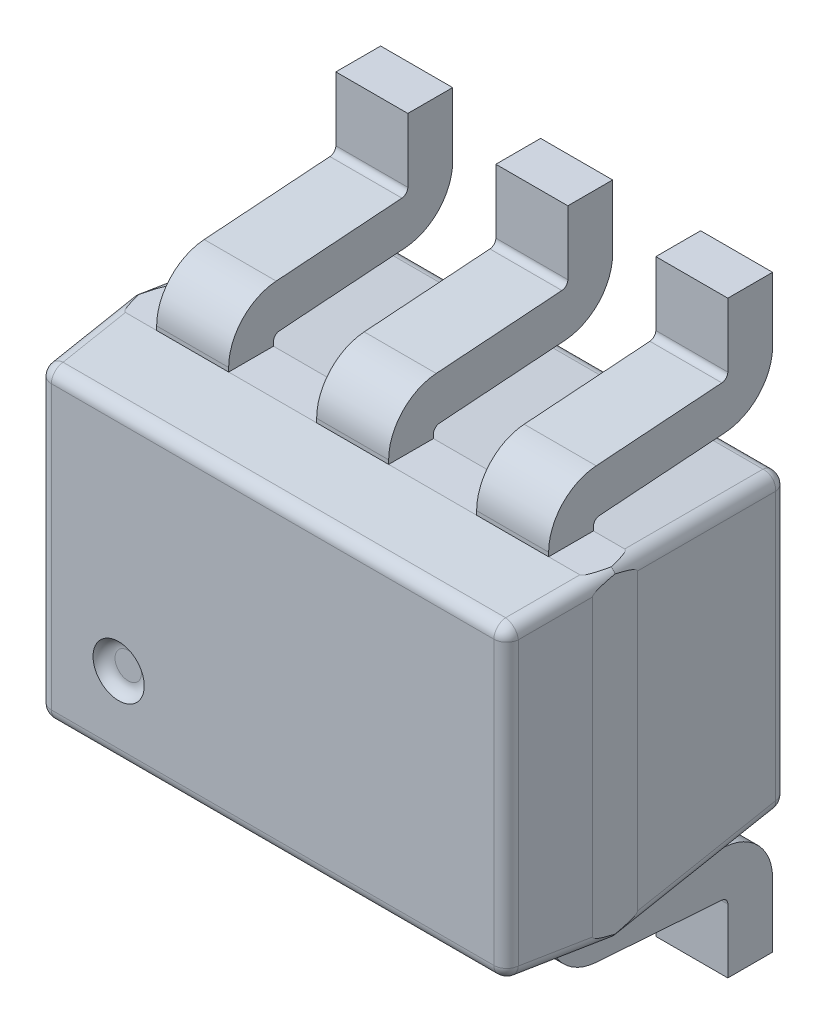
SolidWorks part; units mm, degrees
ref_plane "Alzado" through (0, 0, 0) normal (0, 0, 1) x (1, 0, 0)
ref_plane "Planta" through (0, 0, 0) normal (0, 1, 0) x (1, 0, 0)
ref_plane "Vista lateral" through (0, 0, 0) normal (1, 0, 0) x (0, 0, -1)
sketch "Croquis1" plane through (0, 0, 0) normal (0, 0, 1) x (1, 0, 0)
  line L1 (-0.75, -0.5) -> (0.75, -0.5)
  line L2 (-0.75, -0.5) -> (-0.75, 0.5)
  line L3 (-0.75, 0.5) -> (0.75, 0.5)
  line L4 (0.75, -0.5) -> (0.75, 0.5)
  line L5 (-0.75, -0.5) -> (0.75, 0.5) construction
  line L6 (-0.75, 0.5) -> (0.75, -0.5) construction
  point P0 (0, 0)
  dimension "D1" = 1
  dimension "D2" = 1.5
extrude "Saliente-Extruir1" add sketch "Croquis1" along normal blind 0.51 from offset 0.05
chamfer "Chaflán1" distance 0.51 angle 5 4 edges at (0, 0.5, 0.05) (0, -0.5, 0.05) (-0.75, 0, 0.05) (0.75, 0, 0.05) first distance on face at (0, 0.5, 0.305) first distance on face at (0, -0.5, 0.305) first distance on face at (-0.75, 0, 0.305) first distance on face at (0.75, 0, 0.305)
sketch "Croquis2" plane through (0, 0, 0.56) normal (0, 0, 1) x (1, 0, 0)
  line L1 (-0.75, -0.5) -> (0.75, -0.5)
  line L2 (-0.75, -0.5) -> (-0.75, 0.5)
  line L3 (-0.75, 0.5) -> (0.75, 0.5)
  line L4 (0.75, -0.5) -> (0.75, 0.5)
  line L5 (-0.75, -0.5) -> (0.75, 0.5) construction
  line L6 (-0.75, 0.5) -> (0.75, -0.5) construction
  point P0 (0, 0)
extrude "Saliente-Extruir2" add sketch "Croquis2" along normal blind 0.39
chamfer "Chaflán2" distance 0.25 angle 5 4 edges at (-0.75, 0, 0.95) (0, -0.5, 0.95) (0.75, 0, 0.95) (0, 0.5, 0.95) first distance on face at (-0.75, 0, 0.755) first distance on face at (0, -0.5, 0.755) first distance on face at (0.75, 0, 0.755) first distance on face at (0, 0.5, 0.755)
fillet "Redondeo1" radius 0.04 16 edges at (0, 0.4554, 0.05) (-0.7054, 0, 0.05) (0, -0.4554, 0.05) (0.7054, 0, 0.05) (0.7281, 0, 0.95) (0, -0.4781, 0.95) (-0.7281, 0, 0.95) (0, 0.4781, 0.95) (0.7277, -0.4777, 0.305) (0.7391, -0.4891, 0.825) (0.7391, 0.4891, 0.825) (0.7277, 0.4777, 0.305) (-0.7277, 0.4777, 0.305) (-0.7391, 0.4891, 0.825) (-0.7277, -0.4777, 0.305) (-0.7391, -0.4891, 0.825)
sketch "Croquis4" plane through (0, 0, 0) normal (1, 0, 0) x (0, 0, -1)
  line L0 (-0.56, -0.495) -> (-0.56, -0.5124)
  line L1 (-0.5414, -0.5323) -> (-0.1486, -0.5604)
  line L2 (0, -0.72) -> (0, -0.92)
  line L3 (0, 0) -> (-0.7594, 0) construction
  arc A0 (-0.1486, -0.5604) -> (0, -0.72) centre (-0.16, -0.72) cw
  arc A1 (-0.56, -0.5124) -> (-0.5414, -0.5323) centre (-0.54, -0.5124) ccw
  point P9 (0, -0.571)
  point P12 (-0.56, -0.531)
  dimension "D5" = 0.2
  dimension "D1" = 0.425
  dimension "D2" = 0.16
  dimension "D6" = 0.02
  dimension "D3" = 0.076
  dimension "D4" = 0.04
extrude "Extruir-Lámina1" add sketch "Croquis4" along normal mid plane 0.225 thin thin type one direction wall 0.14
pattern_linear "MatrizL2" count 2 spacing 0.5 along (1, 0, 0) count 2 spacing 0.5 along (-1, 0, 0) of "Extruir-Lámina1"
mirror "Simetría2" about plane through (0, 0, 0) normal (0, 1, 0) of "MatrizL2"
sketch "Croquis7" plane through (0.1125, 0, 0) normal (1, 0, 0) x (0, 0, -1)
  line L1 (-0.7, 0.5) -> (0, 0.5)
  line L2 (-0.7, 0.5) -> (-0.7, 0.92)
  line L3 (-0.7, 0.92) -> (0, 0.92)
  line L4 (0, 0.5) -> (0, 0.92)
extrude "Cortar-Extruir1" cut sketch "Croquis7" against normal blind 0.225
sketch "Croquis8" plane through (0, 0, 0.95) normal (0, 0, 1) x (1, 0, 0)
  line L0 (-0.7313, -0.4415) -> (-0.7313, 0.4415) construction
  line L1 (0.6915, -0.4813) -> (-0.6915, -0.4813) construction
  circle A0 centre (-0.4813, -0.2313) radius 0.08
  dimension "D1" = 0.25
  dimension "D2" = 0.25
extrude "Cortar-Extruir3" cut sketch "Croquis8" against normal blind 0.03
fillet "Redondeo2" radius 0.04 1 edges at (-0.4013, -0.2313, 0.92)
mirror "Mirror1" about plane through (0, 0, 0) normal (0, 1, 0) of "Extruir-Lámina1"
